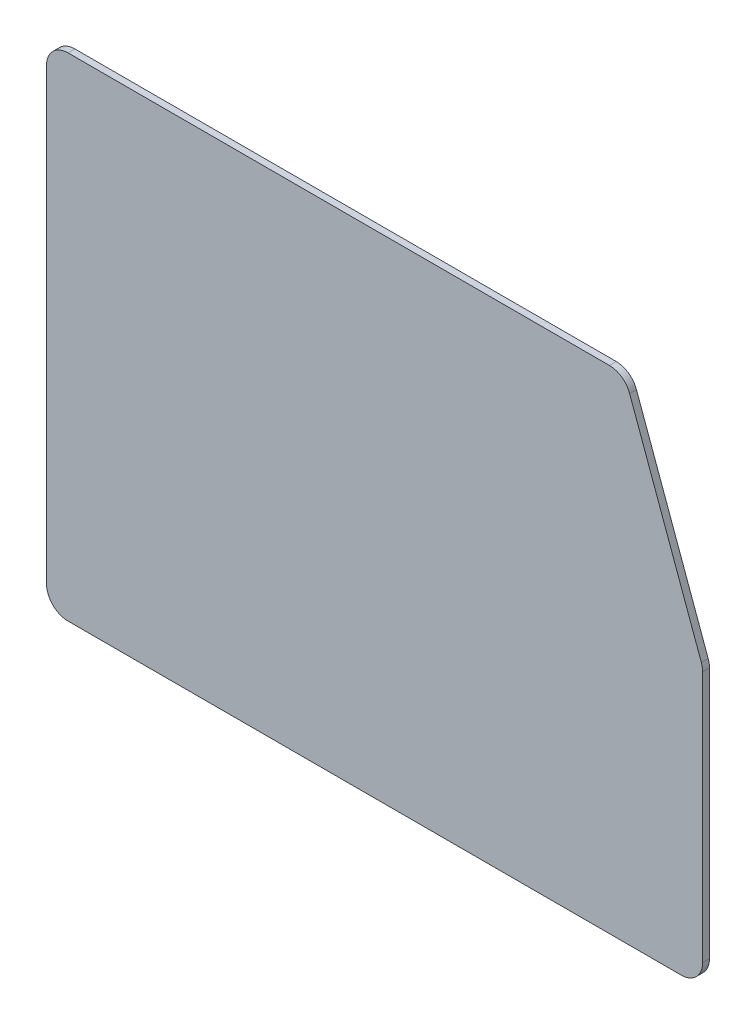
SolidWorks part; units mm, degrees
ref_plane "Front Plane" through (0, 0, 0) normal (0, 0, 1) x (1, 0, 0)
ref_plane "Top Plane" through (0, 0, 0) normal (0, 1, 0) x (1, 0, 0)
ref_plane "Right Plane" through (0, 0, 0) normal (1, 0, 0) x (0, 0, -1)
sketch "Sketch1" plane through (0, 0, 0) normal (0, 0, 1) x (1, 0, 0)
  line L0 (-62.0347, 309.1444) -> (206.4353, 309.1444)
  line L3 (206.4353, 309.1444) -> (242.7653, 209.3286)
  line L4 (242.7653, 209.3286) -> (242.7653, 80.5444)
  line L6 (242.7653, 80.5444) -> (-62.0347, 80.5444)
  line L7 (-62.0347, 80.5444) -> (-62.0347, 309.1444)
  dimension "D1" = 304.8
  dimension "D24" = 106.2217
  dimension "D4" = 228.6
extrude "Boss-Extrude1" add sketch "Sketch1" along normal blind 3.175 contours L0 L3 L4 L6 L7
fillet "Fillet1" radius 10 5 edges at (242.7653, 80.5444, 1.5875) (242.7653, 209.3286, 1.5875) (206.4353, 309.1444, 1.5875) (-62.0347, 80.5444, 1.5875) (-62.0347, 309.1444, 1.5875)
